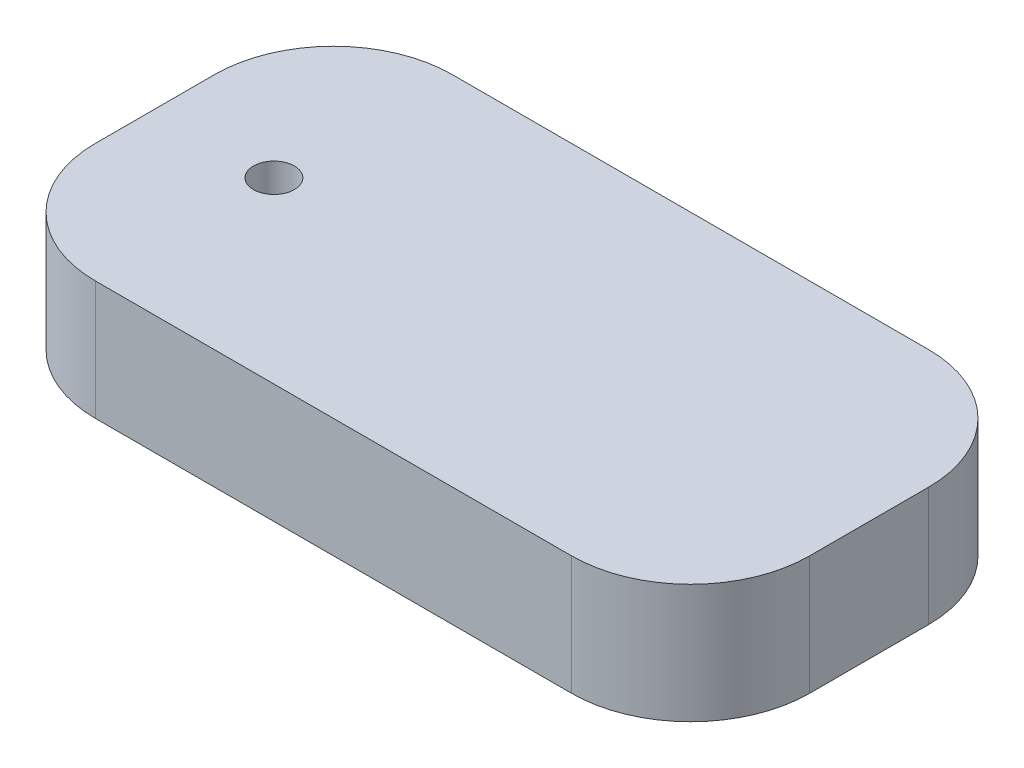
SolidWorks part; units mm, degrees
ref_plane "Front Plane" through (0, 0, 0) normal (0, 0, 1) x (1, 0, 0)
ref_plane "Top Plane" through (0, 0, 0) normal (0, 1, 0) x (1, 0, 0)
ref_plane "Right Plane" through (0, 0, 0) normal (1, 0, 0) x (0, 0, -1)
sketch "Sketch1" plane through (0, 0, 0) normal (0, 1, 0) x (1, 0, 0)
  line L0 (-32.5827, 22.5928) -> (27.4173, 22.5928)
  line L1 (27.4173, 22.5928) -> (27.4173, -7.4072)
  line L2 (-32.5827, 22.5928) -> (-32.5827, -7.4072)
  line L3 (-32.5827, -7.4072) -> (27.4173, -7.4072)
extrude "Boss-Extrude1" add sketch "Sketch1" along normal blind 10
fillet "Fillet1" radius 10 1 edges at (27.4173, 5, 7.4072)
fillet "Fillet2" radius 10 1 edges at (27.4173, 5, -22.5928)
fillet "Fillet3" radius 10 1 edges at (-32.5827, 5, 7.4072)
fillet "Fillet4" radius 10 1 edges at (-32.5827, 5, -22.5928)
sketch "Sketch3" plane through (0, 10, 0) normal (0, 1, 0) x (1, 0, 0)
  line L0 (-22.5827, 22.5928) -> (-22.5827, -7.4072)
  line L1 (-32.5827, 7.5928) -> (27.4173, 7.5928)
  line L2 (-32.5827, 12.5928) -> (-32.5827, 2.5928) construction
  line L3 (27.4173, 2.5928) -> (27.4173, 12.5928) construction
  circle A0 centre (-22.5827, 7.5928) radius 1.7209
  circle A1 centre (-21.2985, 8.7383) radius 52.573
extrude "Cut-Extrude2" cut sketch "Sketch3" against normal blind 7 contours L1 A0 L0 | L1 A0 L0 | A0 region at (-21.8524, 10, -8.3231) region at (-23.3131, 10, -6.8624)
